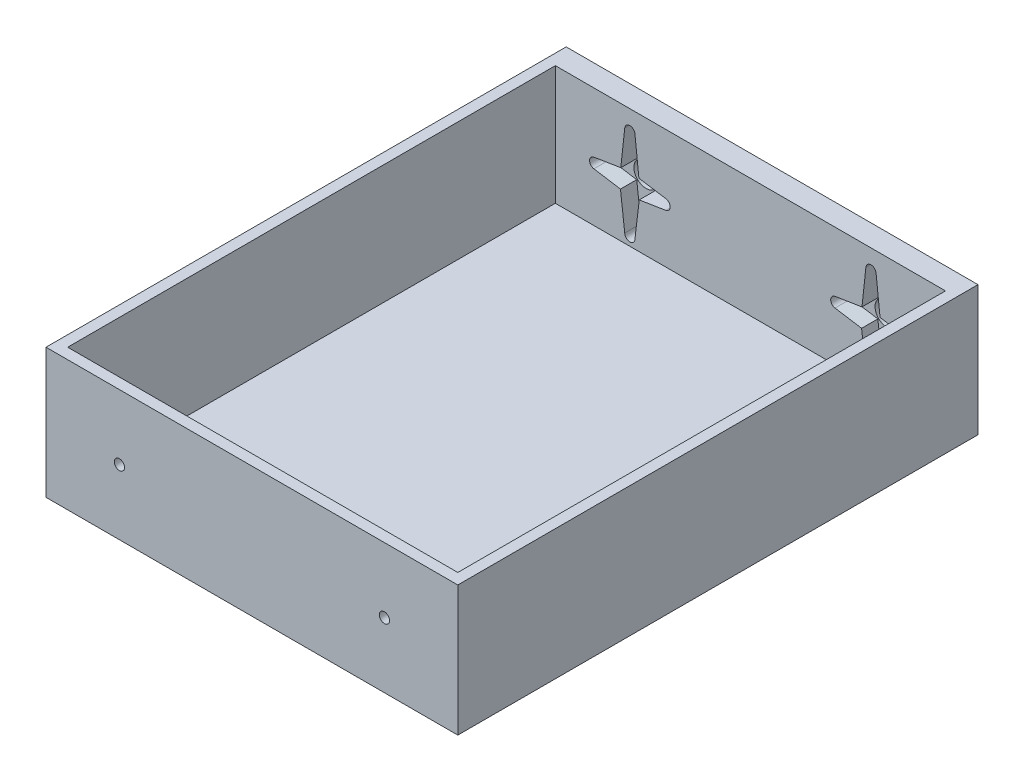
SolidWorks part; units mm, degrees
material "ABS"
ref_plane "Front" through (0, 0, 0) normal (0, 0, 1) x (1, 0, 0)
ref_plane "Top" through (0, 0, 0) normal (0, 1, 0) x (1, 0, 0)
ref_plane "Right" through (0, 0, 0) normal (1, 0, 0) x (0, 0, -1)
sketch "Sketch1" plane through (0, 0, 0) normal (0, 1, 0) x (1, 0, 0)
  line L1 (-60.325, 76.2) -> (60.325, 76.2)
  line L2 (-60.325, 76.2) -> (-60.325, -76.2)
  line L3 (-60.325, -76.2) -> (60.325, -76.2)
  line L4 (60.325, 76.2) -> (60.325, -76.2)
  line L5 (-60.325, 76.2) -> (60.325, -76.2) construction
  line L6 (-60.325, -76.2) -> (60.325, 76.2) construction
  line L11 (-57.15, 69.85) -> (57.15, 69.85)
  line L12 (-57.15, 69.85) -> (-57.15, -73.025)
  line L13 (-57.15, -73.025) -> (57.15, -73.025)
  line L14 (57.15, 69.85) -> (57.15, -73.025)
  point P0 (0, 0)
  point P6 (0, 0)
  dimension "D1" = 3.175
  dimension "D2" = 152.4
  dimension "D3" = 114.3
  dimension "D4" = 3.175
  dimension "D5" = 3.175
  dimension "D6" = 6.35
extrude "Boss-Extrude1" add sketch "Sketch1" along normal blind 3.175 contours L4 L3 L2 L1
extrude "Boss-Extrude2" add sketch "Sketch1<3>" along normal blind 38.1
sketch "Sketch1<3>" plane through (0, 0, 0) normal (0, 1, 0) x (1, 0, 0) same geometry as "Sketch1"
sketch "Sketch2" plane through (0, 0, 76.2) normal (0, 0, 1) x (1, 0, 0)
  line L0 (38.825, 19.05) -> (60.325, 19.05) construction
  line L1 (60.325, 38.1) -> (60.325, 0) construction
  circle A0 centre (38.825, 19.05) radius 1.5
  dimension "D2" = 3
  dimension "D1" = 21.5
extrude "Cut-Extrude1" cut sketch "Sketch2" against normal up to surface (3.175 mm away) up to face at (0, 20.6375, 73.025)
sketch "Sketch3" plane through (0, 0, -69.85) normal (0, 0, 1) x (1, 0, 0)
  line L0 (60.325, 19.05) -> (35.325, 19.05) construction
  line L1 (60.325, 38.1) -> (60.325, 0) construction
  line L2 (36.825, 5.8) -> (38.138, 16.8438)
  line L3 (33.825, 5.8) -> (32.5119, 16.8438)
  line L4 (32.6352, 21.4049) -> (33.8337, 32.4617)
  line L5 (38.0148, 21.4049) -> (36.8163, 32.4617)
  line L6 (24.7882, 17.5688) -> (33.1188, 16.2369)
  line L7 (24.7882, 20.5312) -> (33.1188, 21.863)
  line L9 (33.1188, 21.863) -> (33.1188, 16.2369) construction
  line L10 (37.5312, 21.863) -> (45.8618, 20.5312)
  line L11 (37.5312, 16.237) -> (45.8618, 17.5688)
  arc A0 (32.6352, 21.4049) -> (32.5119, 16.8438) centre (35.325, 19.05) ccw
  arc A1 (33.825, 5.8) -> (36.825, 5.8) centre (35.325, 5.8) ccw
  arc A2 (32.6352, 21.4049) -> (32.5119, 16.8438) centre (35.325, 19.05) ccw construction
  arc A10 (33.8337, 32.4617) -> (36.8163, 32.4617) centre (35.325, 32.3) cw
  arc A11 (38.138, 16.8438) -> (38.0148, 21.4049) centre (35.325, 19.05) ccw
  arc A12 (38.138, 16.8438) -> (38.0148, 21.4049) centre (35.325, 19.05) ccw construction
  arc A13 (24.7882, 20.5312) -> (24.7882, 17.5688) centre (25.025, 19.05) ccw
  arc A14 (37.5312, 21.863) -> (37.5312, 16.237) centre (35.325, 19.05) cw
  arc A15 (33.1188, 16.2369) -> (33.1188, 21.863) centre (35.325, 19.05) cw
  arc A16 (45.8618, 20.5312) -> (45.8618, 17.5688) centre (45.625, 19.05) cw
  circle A17 centre (35.325, 19.05) radius 3.575
  dimension "D1" = 7.15
  dimension "D3" = 3
  dimension "D6" = 14.75
  dimension "D7" = 3
  dimension "D2" = 25
  dimension "D4" = 14.75
  dimension "D5" = 5.6261
  dimension "D8" = 5.6261
  dimension "D9" = 11.8
extrude "Cut-Extrude8" cut sketch "Sketch3" against normal blind 4.7625 contours A16 L10 L5 A11 L2 L11 | A17 L10 L5 A10 L4 L7 | A17 L6 L3 A1 L2 L11 | L4 A15 L7 | L2 A14 L11 | L6 A15 L3 | L6 A15 L7 A13 | A14 L11 A16 L10 region at (35.325, 10.8168, -69.85) region at (37.9239, 16.4606, -69.85) region at (42.2416, 19.0536, -69.85) region at (32.7261, 16.4606, -69.85) region at (35.325, 27.3342, -69.85) region at (32.8048, 21.6911, -69.85)
extrude "Cut-Extrude9" cut sketch "Sketch3<8>" against normal through all contours A14 A17 A15 A0 A11 region at (35.325, 19.05, -69.85)
sketch "Sketch3<8>" plane through (0, 0, -69.85) normal (0, 0, 1) x (1, 0, 0) same geometry as "Sketch3"
mirror "Mirror1" about plane through (0, 0, 0) normal (1, 0, 0) of "Cut-Extrude9", "Cut-Extrude1", "Cut-Extrude8"
